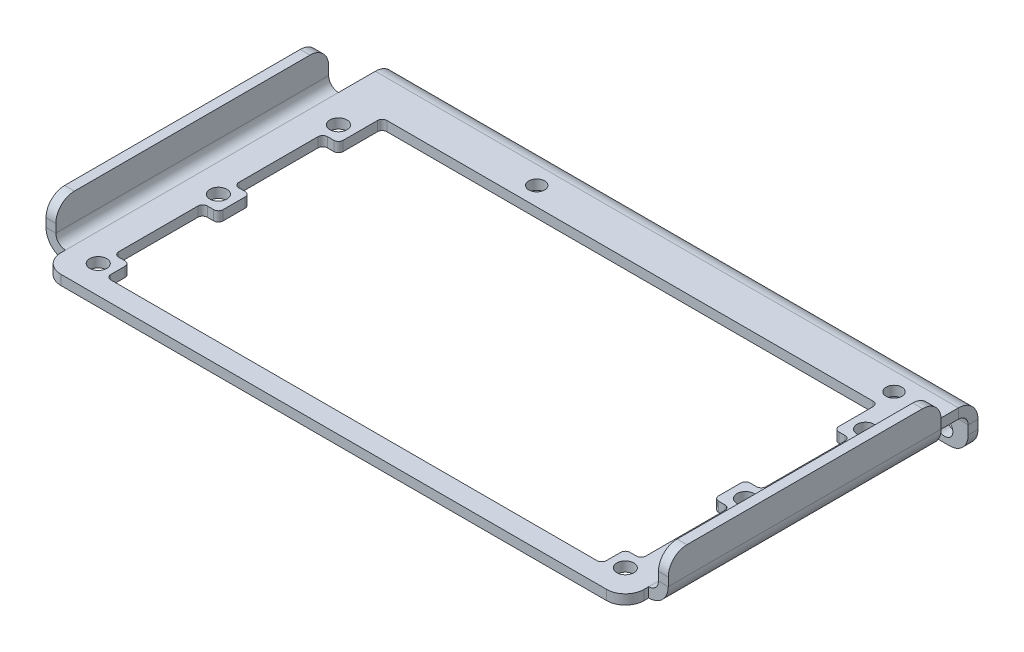
SolidWorks part; units mm, degrees
note: The reader was unsure of these and kept them because the rebuilt part matched: flange length of "Edge-Flange1", "Edge-Flange2".
ref_plane "Front Plane" through (0, 0, 0) normal (0, 0, 1) x (1, 0, 0)
ref_plane "Top Plane" through (0, 0, 0) normal (0, 1, 0) x (1, 0, 0)
ref_plane "Right Plane" through (0, 0, 0) normal (1, 0, 0) x (0, 0, -1)
sketch "Sketch1" plane through (0, 0, 0) normal (0, 1, 0) x (1, 0, 0)
  line L0 (0, 63.5) -> (125, 63.5) construction
  line L1 (0, 0) -> (125, 0)
  line L2 (0, 0) -> (0, 73.5)
  line L3 (0, 73.5) -> (125, 73.5)
  line L4 (125, 0) -> (125, 73.5)
  dimension "D1" = 125
  dimension "D2" = 10
base flange "Base-Flange1" sketch "Sketch1" thickness 2.1 reverse thickness direction no parameters "D1"=2.1
edge flange "Edge-Flange1" sketch "Sketch4" flange angle 90 flange length 8 flange position material outside bend radius 2.1 thickness 2.1 relief rectangular parameters "D6"=10
sketch "Sketch4" plane through (0, -2.1, -73.5) normal (0, 0, -1) x (1, 0, 0)
  line L2 (0, 0) -> (0, 8)
  line L3 (0, 8) -> (125, 8)
  line L4 (125, 8) -> (125, 0)
  line L7 (125, 0) -> (0, 0) construction
  line L8 (125, 0) -> (0, 0)
bend "EdgeBend1" bend radius 2.1 bend angle 90 parameters "D5"=1
sketch "Sketch7" plane through (0, -2.1, 0) normal (0, -1, 0) x (-1, 0, 0)
  line L0 (-6, 9.375) -> (-6, 54.125) construction
  line L1 (-6, 54.125) -> (-9.375, 54.125)
  line L2 (-9.375, 54.125) -> (-9.375, 63.5)
  line L3 (-9.375, 63.5) -> (-115.625, 63.5)
  line L4 (-115.625, 63.5) -> (-115.625, 54.125)
  line L5 (-115.625, 54.125) -> (-119, 54.125)
  line L6 (-119, 54.125) -> (-119, 9.375) construction
  line L7 (-119, 9.375) -> (-115.625, 9.375)
  line L8 (-115.625, 9.375) -> (-115.625, 4.3)
  line L9 (-115.625, 4.3) -> (-9.375, 4.3)
  line L10 (-9.375, 4.3) -> (-9.375, 9.375)
  line L11 (-9.375, 9.375) -> (-6, 9.375)
  line L12 (0, 0) -> (-125, 0) construction
  line L13 (0, 71.4) -> (0, 0) construction
  line L14 (-125, 0) -> (-125, 71.4) construction
  line L15 (68.1321, 63.5) -> (-41.8679, 63.5) construction
  line L16 (-6, 9.375) -> (-6, 28.375)
  line L17 (-6, 28.375) -> (-9.375, 28.375)
  line L18 (-6, 28.375) -> (-6, 35.125)
  line L19 (-6, 35.125) -> (-9.375, 35.125)
  line L20 (-9.375, 28.375) -> (-9.375, 35.125)
  line L21 (-115.625, 28.375) -> (-119, 28.375)
  line L22 (-115.625, 28.375) -> (-115.625, 35.125)
  line L23 (-115.625, 35.125) -> (-119, 35.125)
  line L24 (-119, 28.375) -> (-119, 35.125)
  line L25 (-6, 35.125) -> (-6, 54.125)
  line L26 (-119, 54.125) -> (-119, 35.125)
  line L27 (-119, 28.375) -> (-119, 9.375)
  point P21 (-7.6875, 54.125)
  point P27 (-6, 31.75)
  point P28 (-6, 31.75)
  point P29 (23.4118, 16.3649)
  point P30 (-119, 31.75)
  point P35 (-119, 31.75)
  dimension "D1" = 4.3
  dimension "D2" = 6
  dimension "D3" = 6
  dimension "D4" = 3.375
  dimension "D5" = 3.375
  dimension "D6" = 3.375
  dimension "D7" = 6.75
  dimension "D10" = 3.375
extrude "Cut-Extrude1" cut sketch "Sketch7" against normal up to next contours L21 L27 L7 L8 L9 L10 L11 L16 L17 L20 L19 L25 L1 L2 L3 L4 L5 L26 L23 L22 normal cut yes
hole_wizard "psu-mounting-holes" positions "Sketch5" profile "Sketch6" hole size "#27" standard "ANSI Inch" end condition up to next
sketch "Sketch5" plane through (0, 0, 0) normal (0, 1, 0) x (1, 0, 0)
  point P2 (119, 6)
  point P5 (119, 57.5)
  point P8 (6, 6)
  point P16 (6, 57.5)
  point P22 (6, 31.75)
  point P24 (119, 31.75)
sketch "Sketch6" plane through (119, 0, -6) normal (1, 0, 0) x (0, 0, 1)
  line L0 (0, 0) -> (0, 2.1)
  line L1 (0, 2.1) -> (1.8288, 2.1)
  line L2 (1.8288, 2.1) -> (1.8288, 0)
  line L5 (1.8288, 0) -> (0, 0)
  line L11 (0, -6.35) -> (0, 107.95) construction
  dimension "Thru Hole Dia." = 3.6576
  dimension "Thru Hole Depth" = 2.1
fillet "Fillet1" radius 1 20 edges at (115.625, -1.05, -4.3) (119, -1.05, -9.375) (115.625, -1.05, -9.375) (119, -1.05, -28.375) (115.625, -1.05, -28.375) (119, -1.05, -35.125) (115.625, -1.05, -35.125) (119, -1.05, -54.125) (115.625, -1.05, -54.125) (115.625, -1.05, -63.5) (9.375, -1.05, -63.5) (6, -1.05, -54.125) (9.375, -1.05, -54.125) (6, -1.05, -35.125) (9.375, -1.05, -35.125) (9.375, -1.05, -28.375) (6, -1.05, -28.375) (9.375, -1.05, -4.3) (9.375, -1.05, -9.375) (6, -1.05, -9.375)
hole_wizard "ssd-mounting-holes" positions "Sketch8" profile "Sketch9" hole size "M3" standard "ANSI Metric" end condition up to next
sketch "Sketch8" plane through (0, 0, 0) normal (0, 1, 0) x (1, 0, 0)
  point P0 (115.1, 67.5)
  point P3 (38.5, 67.5)
sketch "Sketch9" plane through (115.1, 0, -67.5) normal (1, 0, 0) x (0, 0, 1)
  line L0 (0, 0) -> (0, 2.1)
  line L1 (0, 2.1) -> (1.7, 2.1)
  line L2 (1.7, 2.1) -> (1.7, 0)
  line L5 (1.7, 0) -> (0, 0)
  line L11 (0, -6.35) -> (0, 107.95) construction
  dimension "Thru Hole Dia." = 3.4
  dimension "Thru Hole Depth" = 2.1
sketch "Sketch10" plane through (0, 0, -73.5) normal (0, 0, 1) x (1, 0, 0)
  line L0 (125, -7.15) -> (120, -7.15) construction
  line L1 (125, -4.2) -> (125, -10.1) construction
  line L2 (0, -7.15) -> (5, -7.15) construction
  line L3 (0, -10.1) -> (0, -4.2) construction
  dimension "D1" = 5
hole_wizard "M3 Clearance Hole1" positions "Sketch11" profile "Sketch12" hole size "M3" standard "ANSI Metric" end condition through all
sketch "Sketch11" plane through (0, 0, -73.5) normal (0, 0, 1) x (1, 0, 0)
  point P0 (120, -7.15)
  point P3 (5, -7.15)
sketch "Sketch12" plane through (120, -7.15, -73.5) normal (1, 0, 0) x (0, -1, 0)
  line L0 (0, 0) -> (0, 2.1)
  line L1 (0, 2.1) -> (1.7, 2.1)
  line L2 (1.7, 2.1) -> (1.7, 0)
  line L5 (1.7, 0) -> (0, 0)
  line L11 (0, -6.35) -> (0, 107.95) construction
  dimension "Thru Hole Dia." = 3.4
  dimension "Thru Hole Depth" = 2.1
edge flange "Edge-Flange2" sketch "Sketch17" flange profiles "Sketch17", "Sketch18" flange angle 90 flange length 10 flange position bend outside bend radius 2.1 thickness 2.1 relief rectangular parameters "D6"=10, "D8"=1
sketch "Sketch17" plane through (125, 0, 0) normal (1, 0, 0) x (0, 0, -1)
  line L2 (5, 0) -> (5, 7.9)
  line L3 (5, 7.9) -> (63.5, 7.9)
  line L4 (63.5, 7.9) -> (63.5, 0)
  line L15 (63.5, -2.1) -> (63.5, 0) construction
  line L19 (0, 0) -> (71.4, 0) construction
  line L20 (5, 0) -> (63.5, 0)
  line L21 (0, -2.1) -> (0, 0) construction
  dimension "D1" = 5
  dimension "D2" = 0
sketch "Sketch18" plane through (0, 0, 0) normal (-1, 0, 0) x (0, 0, 1)
  line L0 (-63.5, 0) -> (-63.5, -2.1) construction
  line L2 (-63.5, 0) -> (-63.5, 7.9)
  line L3 (-63.5, 7.9) -> (-5, 7.9)
  line L4 (-5, 7.9) -> (-5, 0)
  line L7 (-71.4, 0) -> (0, 0) construction
  line L8 (-63.5, 0) -> (-5, 0)
  line L9 (0, -2.1) -> (0, 0) construction
  dimension "D1" = 5
  dimension "D2" = 0
bend "EdgeBend2" bend radius 2.1 bend angle 90 parameters "D5"=2
bend "EdgeBend3" bend radius 2.1 bend angle 90 parameters "D5"=3
fillet "Fillet2" radius 4 8 edges at (125, -10.1, -74.55) (0, -10.1, -74.55) (0, -1.05, 0) (125, -1.05, 0) (-3.15, 7.9, -5) (-3.15, 7.9, -63.5) (128.15, 7.9, -63.5) (128.15, 7.9, -5)
sketch "Bend-Lines1" [suppressed] plane through (0, 0, 0) normal (0, 1, 0) x (1, 0, 0)
sketch "Bounding-Box1" [suppressed] plane through (0, 0, 0) normal (0, 1, 0) x (1, 0, 0)
fillet "Fillet3" [suppressed] radius 1
sheet metal parameters "Sheet-Metal12" thickness 2.1 parameters "D1"=1.016
flat pattern "Flat-Pattern12" [suppressed]
sketch "Bend-Lines2" plane through (0, 0, 0) normal (0, 1, 0) x (1, 0, 0)
sketch3d "Bounding-Box2" [suppressed]
  line L0 (-125, 47.2236, 0) -> (0, 47.2236, 0) construction
  line L1 (-125, 0, 0) -> (0, 0, 0) construction
  line L2 (-125, 47.2236, 0) -> (-125, 0, 0) construction
  line L3 (0, 47.2236, 0) -> (0, 0, 0) construction
sheet metal parameters "Sheet-Metal13" thickness 2.1 parameters "D1"=1.016
flat pattern "Flat-Pattern12"
sketch "Bend-Lines2" plane through (0, 0, 0) normal (0, 1, 0) x (1, 0, 0)
  line L0 (125, 72.6649) -> (0, 72.6649) construction
  line L1 (125, 72.6649) -> (0, 72.6649) construction
sketch3d "Bounding-Box2" [suppressed]
  line L0 (125, 80.8459, 0) -> (0, 80.8459, 0) construction
  line L1 (125, 0, 0) -> (0, 0, 0) construction
  line L2 (125, 80.8459, 0) -> (125, 0, 0) construction
  line L3 (0, 80.8459, 0) -> (0, 0, 0) construction
bend of the flat pattern "Flatten-<EdgeBend1>1"
sheet metal parameters "Sheet-Metal14" thickness 2.1 parameters "D1"=1.016
flat pattern "Flat-Pattern12"
sketch "Bend-Lines2" plane through (0, 0, 0) normal (0, 1, 0) x (1, 0, 0)
  line L0 (125, 72.6649) -> (0, 72.6649) construction
  line L1 (125, 72.6649) -> (0, 72.6649) construction
sketch3d "Bounding-Box2" [suppressed]
  line L0 (125, 80.8459, 0) -> (0, 80.8459, 0) construction
  line L1 (125, 0, 0) -> (0, 0, 0) construction
  line L2 (125, 80.8459, 0) -> (125, 0, 0) construction
  line L3 (0, 80.8459, 0) -> (0, 0, 0) construction
bend of the flat pattern "Flatten-<EdgeBend1>1"
sheet metal parameters "Sheet-Metal15" thickness 2.1 parameters "D1"=1.016
flat pattern "Flat-Pattern12"
sketch "Bend-Lines2" plane through (0, 0, 0) normal (0, 1, 0) x (1, 0, 0)
  line L0 (125, 72.6649) -> (0, 72.6649) construction
  line L1 (125, 72.6649) -> (0, 72.6649) construction
sketch3d "Bounding-Box2" [suppressed]
  line L0 (125, 80.8459, 0) -> (0, 80.8459, 0) construction
  line L1 (125, 0, 0) -> (0, 0, 0) construction
  line L2 (125, 80.8459, 0) -> (125, 0, 0) construction
  line L3 (0, 80.8459, 0) -> (0, 0, 0) construction
bend of the flat pattern "Flatten-<EdgeBend1>1"
sheet metal parameters "Sheet-Metal16" thickness 2.1 parameters "D1"=1.016
flat pattern "Flat-Pattern12"
sketch "Bend-Lines2" plane through (0, 0, 0) normal (0, 1, 0) x (1, 0, 0)
  line L0 (125, 72.6649) -> (0, 72.6649) construction
  line L1 (125, 72.6649) -> (0, 72.6649) construction
sketch3d "Bounding-Box2" [suppressed]
  line L0 (125, 80.8459, 0) -> (0, 80.8459, 0) construction
  line L1 (125, 0, 0) -> (0, 0, 0) construction
  line L2 (125, 80.8459, 0) -> (125, 0, 0) construction
  line L3 (0, 80.8459, 0) -> (0, 0, 0) construction
bend of the flat pattern "Flatten-<EdgeBend1>1"
sheet metal parameters "Sheet-Metal17" thickness 2.1 parameters "D1"=1.016
flat pattern "Flat-Pattern12" [suppressed]
sketch "Bend-Lines2" plane through (0, 0, 0) normal (0, 1, 0) x (1, 0, 0)
  line L0 (125, 71.6091) -> (0, 71.6091) construction
  line L1 (125, 71.6091) -> (0, 71.6091) construction
sketch3d "Bounding-Box2" [suppressed]
  line L0 (0, 79.8181, 0) -> (125, 79.8181, 0) construction
  line L1 (0, 0, 0) -> (125, 0.0001, 0) construction
  line L2 (0, 79.8181, 0) -> (0, 0, 0) construction
  line L3 (125, 79.8181, 0) -> (125, 0.0001, 0) construction
bend of the flat pattern "Flatten-<EdgeBend1>1"
sketch "Sketch10-1" plane through (0, -2.1, -69.7181) normal (0, -1, 0) x (1, 0, 0)
  line L0 (125, -7.15) -> (120, -7.15) construction
  line L2 (0, -7.15) -> (5, -7.15) construction
  dimension "D1" = 5
sheet metal parameters "Sheet-Metal26" thickness 2.1 parameters "D1"=1.016
flat pattern "Flat-Pattern12" [suppressed]
sketch "Bend-Lines2" plane through (0, 0, 0) normal (0, 1, 0) x (1, 0, 0)
  line L0 (125, 73.7091) -> (0, 73.7091) construction
  line L1 (125, 73.7091) -> (0, 73.7091) construction
  line L2 (-2.3091, 63.5) -> (-2.3091, 5) construction
  line L3 (127.3091, 5) -> (127.3091, 63.5) construction
  line L4 (-2.3091, 63.5) -> (-2.3091, 5) construction
  line L5 (127.3091, 5) -> (127.3091, 63.5) construction
sketch3d "Bounding-Box2" [suppressed]
  line L0 (-10.4182, 81.918, 0) -> (135.4181, 81.9182, 0) construction
  line L1 (-10.4181, 0, 0) -> (135.4182, 0.0001, 0) construction
  line L2 (-10.4182, 81.918, 0) -> (-10.4181, 0, 0) construction
  line L3 (135.4181, 81.9182, 0) -> (135.4182, 0.0001, 0) construction
bend of the flat pattern "Flatten-<EdgeBend1>1"
bend of the flat pattern "Flatten-<EdgeBend2>1"
bend of the flat pattern "Flatten-<EdgeBend3>1"
sketch "Sketch10-1" plane through (0, -2.1, -71.8181) normal (0, -1, 0) x (1, 0, 0)
  line L0 (125, -7.15) -> (120, -7.15) construction
  line L2 (0, -7.15) -> (5, -7.15) construction
  dimension "D1" = 5
equation "\"ssd-clearance\"= 12mm"
equation "\"psu-height\"= 63.5mm"
